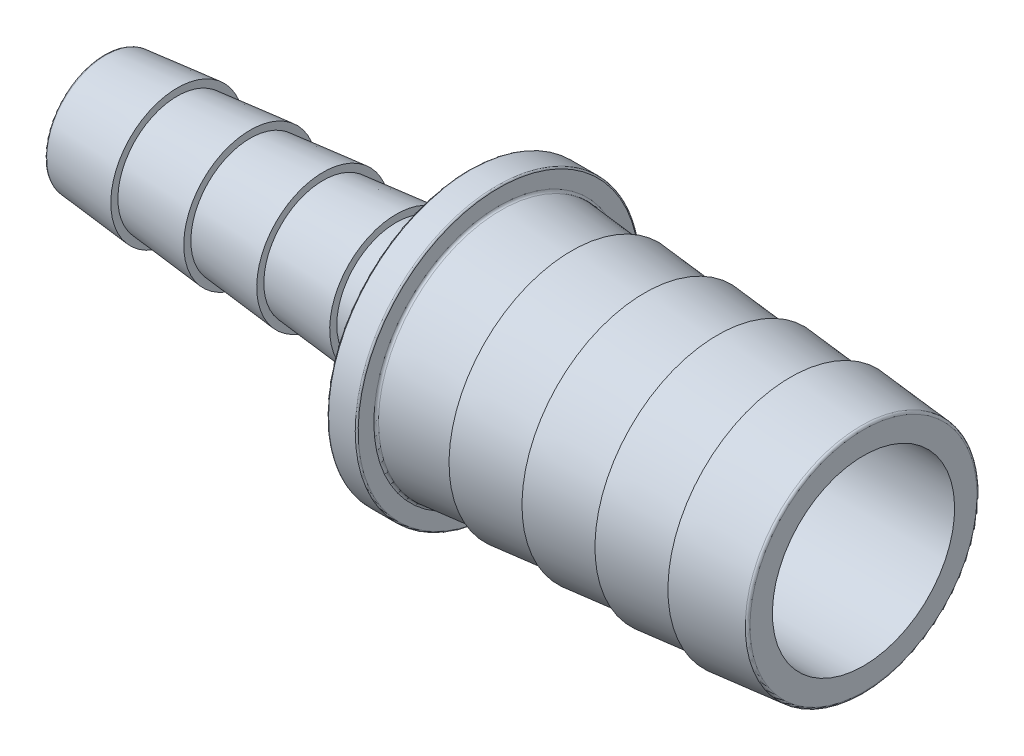
SolidWorks part; units mm, degrees
note: '?' marks a value the reader was unsure of.
other "Camera1"
ref_plane "Front Plane" through (0, 0, 0) normal (0, 0, 1) x (1, 0, 0)
ref_plane "Top Plane" through (0, 0, 0) normal (0, 1, 0) x (1, 0, 0)
ref_plane "Right Plane" through (0, 0, 0) normal (1, 0, 0) x (0, 0, -1)
sketch "Sketch1" plane through (0, 0, 0) normal (0, 0, 1) x (1, 0, 0)
  line L0 (-25.4, 4.445) -> (-25.4, -4.445) construction
  line L1 (-25.4, 0) -> (25.4, 0) construction
  line L2 (25.4, 8.2042) -> (25.4, -8.2042) construction
  line L3 (-0.9906, 9.4996) -> (-0.9906, -9.4996) construction
  line L4 (0.9906, -9.4996) -> (-0.9906, -9.4996) construction
  line L5 (0.9906, -9.4996) -> (0.9906, 9.4996) construction
  line L6 (0.9906, 9.4996) -> (-0.9906, 9.4996) construction
  line L7 (-25.4, 3.9688) -> (-25.4, -3.9688) construction
  line L8 (-25.4, -2.54) -> (-25.4, 2.54) construction
  line L9 (25.4, 7.747) -> (25.4, -7.747) construction
  line L10 (25.4, 6.096) -> (25.4, -6.096) construction
  point P7 (25.4, 0)
  point P8 (0, 0)
  point P15 (0.9906, 0)
  point P19 (-25.4, 0)
  point P20 (-25.4, 0)
  point P25 (25.4, 0)
  point P26 (25.4, 0)
  dimension "D4" = 1.4287
  dimension "D8" = 1.651
sketch "Sketch2" plane through (0, 0, 0) normal (0, 0, 1) x (1, 0, 0)
  line L0 (-25.4, 3.9688) -> (-5.8725, 3.9688)
  line L1 (-0.9906, 9.4996) -> (-0.9906, -9.4996) construction
  line L2 (-0.9906, 4.445) -> (-0.9906, 9.4996)
  line L3 (-0.9906, 9.4996) -> (0.9906, 9.4996)
  line L4 (0.9906, 9.4996) -> (0.9906, 8.2042)
  line L5 (0.9906, -9.4996) -> (0.9906, 9.4996) construction
  line L6 (25.4, 7.747) -> (5.8725, 7.747)
  line L7 (25.4, 7.747) -> (25.4, 6.096)
  line L8 (25.4, 6.096) -> (0.9906, 6.096)
  line L9 (-25.4, 3.9688) -> (-25.4, 2.54)
  line L10 (-25.4, 2.54) -> (-0.9906, 2.54)
  line L11 (-5.8725, 3.9688) -> (-0.9906, 4.445)
  line L12 (5.8725, 7.747) -> (0.9906, 8.2042)
  line L13 (-0.9906, 2.54) -> (0.9906, 6.096)
  dimension "D1" = 4.8819
  dimension "D2" = 4.8819
revolve "Revolve1" add sketch "Sketch2" angle 360 about L1
sketch "Sketch3" plane through (0, 0, 0) normal (0, 0, 1) x (1, 0, 0)
  line L0 (-25.4, 3.9688) -> (-20.5181, 3.9688)
  line L1 (-5.8725, 3.9688) -> (-25.4, 3.9688) construction
  line L2 (-20.5181, 3.9688) -> (-20.5181, 4.445)
  line L3 (-20.5181, 4.445) -> (-25.4, 3.9688)
  dimension "D2" = 4.8819
revolve "Revolve2" add sketch "Sketch3" angle 360 about L1
pattern_linear "LPattern1" count 4 spacing 4.8819 along (1, 0, 0) of "Revolve2"
sketch "Sketch4" plane through (0, 0, 0) normal (0, 0, 1) x (1, 0, 0)
  line L0 (25.4, 7.747) -> (20.5181, 7.747)
  line L1 (25.4, 7.747) -> (5.8725, 7.747) construction
  line L2 (20.5181, 7.747) -> (20.5181, 8.2042)
  line L3 (20.5181, 8.2042) -> (25.4, 7.747)
  dimension "D1" = 4.8819
revolve "Revolve3" add sketch "Sketch4" angle 360 about L1
pattern_linear "LPattern2" count 4 spacing 4.8819 along (-1, 0, 0) of "Revolve3"
fillet "Fillet1" radius 0.0991 2 edges at (0.9906, -9.4996, 0) (-0.9906, -9.4996, 0)
fillet "Fillet2" radius 0.1429 2 edges at (-25.4, -3.9688, 0) (-0.9906, -4.445, 0)
fillet "Fillet3" radius 0.1651 2 edges at (25.4, -7.747, 0) (0.9906, -8.2042, 0)
ref_axis "Center Axis 1" through (-27.94, 0, 0) along (1, 0, 0)?
ref_plane "Contact Plane 1" through (0.9906, 0, 0) normal (1, 0, 0) x (0, 0, -1)
ref_plane "Contact Plane 2" through (-0.9906, 0, 0) normal (1, 0, 0) x (0, 0, -1)
equation "\"D1@Sketch2\"=\"D2@Sketch3\""
equation "\"D2@Sketch2\"=\"D1@Sketch4\""
equation "\"D2@Sketch3\"=\"Barb Length A@Sketch1\"/ (\"No. of Barbs: A@LPattern1\"+1)"
equation "\"D3@LPattern1\"=\"D2@Sketch3\""
equation "\"D1@Sketch4\"=\"Barb Length B@Sketch1\"/ (\"No. of Barbs: B@LPattern2\"+1)"
equation "\"D3@LPattern2\"=\"D1@Sketch4\""
equation "\"D1@Fillet1\"=\"Hex Length@Sketch1\"*.05"
equation "\"D1@Fillet2\"=\"D4@Sketch1\"*.1"
equation "\"D1@Fillet3\"=\"D8@Sketch1\"*.1"
